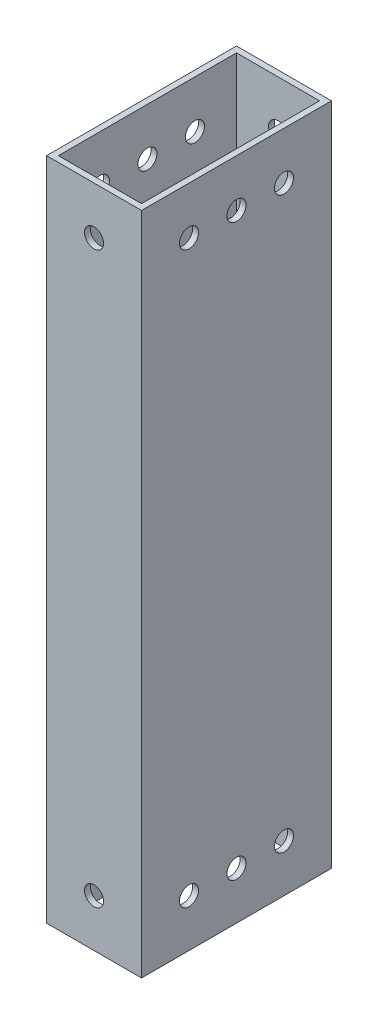
SolidWorks part; units mm, degrees
material "6061-T6 (SS)"
ref_plane "Front" through (0, 0, 0) normal (0, 0, 1) x (1, 0, 0)
ref_plane "Top" through (0, 0, 0) normal (0, 1, 0) x (1, 0, 0)
ref_plane "Right" through (0, 0, 0) normal (1, 0, 0) x (0, 0, -1)
sketch "Sketch1" plane through (0, 0, 0) normal (0, 1, 0) x (1, 0, 0)
  line L1 (12.7, 25.4) -> (-12.7, 25.4)
  line L2 (12.7, 25.4) -> (12.7, -25.4)
  line L3 (12.7, -25.4) -> (-12.7, -25.4)
  line L4 (-12.7, 25.4) -> (-12.7, -25.4)
  line L5 (12.7, 25.4) -> (-12.7, -25.4) construction
  line L6 (12.7, -25.4) -> (-12.7, 25.4) construction
  point P0 (0, 0)
  dimension "D1" = 25.4
  dimension "D2" = 50.8
extrude "Extrude-Thin1" add sketch "Sketch1" along normal blind 177.8 thin thin type one direction reverse wall 1.5875
sketch "Sketch4" plane through (-12.7, 0, 0) normal (-1, 0, 0) x (0, 0, 1)
  line L0 (-12.7, 12.7) -> (12.7, 12.7) construction
  line L3 (-25.4, 0) -> (25.4, 0) construction
  line L4 (-12.7, 165.1) -> (12.7, 165.1) construction
  line L5 (-25.4, 177.8) -> (25.4, 177.8) construction
  point P0 (-12.7, 12.7)
  point P2 (0, 12.7)
  point P4 (12.7, 12.7)
  point P16 (-12.7, 165.1)
  point P17 (12.7, 165.1)
  point P22 (0, 165.1)
  point P30 (-12.7, 165.1)
  point P32 (12.7, 165.1)
  dimension "D1" = 12.7
  dimension "D2" = 12.7
  dimension "D3" = 12.7
hole_wizard "#10 Clearance Hole1" positions "Sketch4" profile "Sketch3" hole size "#10" standard "ANSI Inch" end condition through all
sketch "Sketch3" plane through (-12.7, 12.7, -12.7) normal (0, 1, 0) x (0, 0, 1)
  line L0 (0, 0) -> (0, 25.4)
  line L1 (0, 25.4) -> (2.5527, 25.4)
  line L2 (2.5527, 25.4) -> (2.5527, 0)
  line L5 (2.5527, 0) -> (0, 0)
  line L11 (0, -6.35) -> (0, 107.95) construction
  dimension "Thru Hole Dia." = 5.1054
  dimension "Thru Hole Depth" = 25.4
sketch "Sketch7" plane through (0, 0, 25.4) normal (0, 0, 1) x (1, 0, 0)
  line L0 (-12.7, 0) -> (12.7, 0) construction
  line L1 (-12.7, 177.8) -> (12.7, 177.8) construction
  point P0 (0, 12.7)
  point P2 (0, 165.1)
  dimension "D1" = 12.7
  dimension "D2" = 12.7
hole_wizard "#10 Clearance Hole2" positions "Sketch7" profile "Sketch6" hole size "#10" standard "ANSI Inch" end condition through all
sketch "Sketch6" plane through (0, 12.7, 25.4) normal (1, 0, 0) x (0, -1, 0)
  line L0 (0, 0) -> (0, 50.8)
  line L1 (0, 50.8) -> (2.5527, 50.8)
  line L2 (2.5527, 50.8) -> (2.5527, 0)
  line L5 (2.5527, 0) -> (0, 0)
  line L11 (0, -6.35) -> (0, 107.95) construction
  dimension "Thru Hole Dia." = 5.1054
  dimension "Thru Hole Depth" = 50.8
